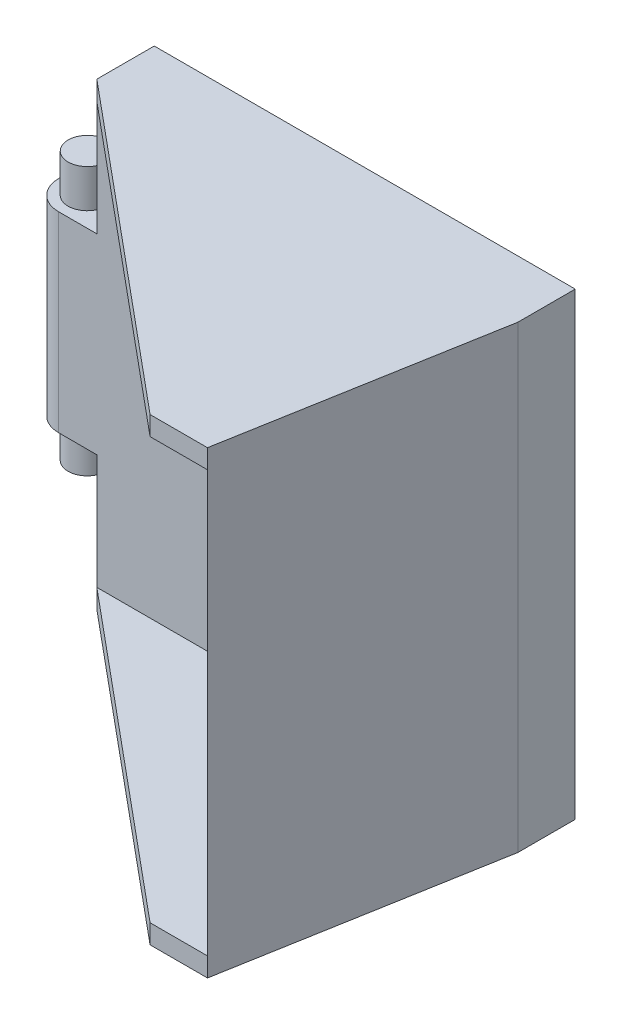
SolidWorks part; units mm, degrees
ref_plane "前视基准面" through (0, 0, 0) normal (0, 0, 1) x (1, 0, 0)
ref_plane "上视基准面" through (0, 0, 0) normal (0, 1, 0) x (1, 0, 0)
ref_plane "右视基准面" through (0, 0, 0) normal (1, 0, 0) x (0, 0, -1)
sketch "草图1" plane through (0, 0, 0) normal (0, 1, 0) x (1, 0, 0)
  line L0 (0, 0) -> (120, 0)
  line L1 (0, 15) -> (120, 15)
  line L7 (120, 15) -> (120, 0)
  arc A1 (0, 0) -> (0, 15) centre (0, 7.5) cw
  circle A3 centre (0, 7.5) radius 5
extrude "凸台-拉伸1" add sketch "草图1" along normal blind 42.5 and the other way blind 7.5
ref_plane "基准面4" through (0, 17.5, 0) normal (0, 1, 0) x (1, 0, 0)
sketch "草图2" plane through (0, 0, 0) normal (0, 1, 0) x (1, 0, 0)
  circle A0 centre (0, 7.5) radius 5
extrude "凸台-拉伸2" add sketch "草图2" against normal mid plane 35
ref_plane "基准面5" through (0, 17.5, 0) normal (0, 1, 0) x (1, 0, 0)
ref_plane "基准面6" through (0, 52.5, 0) normal (0, 1, 0) x (1, 0, 0)
sketch "草图3" plane through (0, 0, 0) normal (0, 1, 0) x (1, 0, 0)
  circle A0 centre (0, 7.5) radius 5
extrude "凸台-拉伸3" add sketch "草图3" along normal up to surface (52.5 mm away) up to plane "基准面6"
ref_plane "基准面7" through (0, 27.5, 0) normal (0, -1, 0) x (-1, 0, 0)
ref_plane "基准面8" through (0, 7.5, 0) normal (0, 1, 0) x (1, 0, 0)
ref_plane "基准面9" through (10, 0, 0) normal (1, 0, 0) x (0, 0, -1)
sketch "草图5" plane through (0, 0, 0) normal (0, 1, 0) x (1, 0, 0)
  line L1 (10, 0) -> (120, 0)
  line L2 (10, 0) -> (10, 15)
  line L3 (10, 15) -> (120, 15)
  line L4 (120, 0) -> (120, 15)
extrude "凸台-拉伸4" add sketch "草图5" along normal blind 77.5 and the other way blind 42.5 contours L1 L4 L3 L2
sketch "草图9" plane through (0, 77.5, 0) normal (0, 1, 0) x (1, 0, 0)
  line L1 (107.8446, -68.9365) -> (92.8446, -68.9365)
  line L2 (92.8446, -68.9365) -> (105, 0)
  line L3 (10, 0) -> (120, 0) construction
  line L4 (105, 0) -> (120, 0)
  line L5 (120, 0) -> (107.8446, -68.9365)
extrude "凸台-拉伸6" add sketch "草图9" against normal up to surface (120 mm away) up to face at (65, -42.5, -7.5)
sketch "草图11" plane through (0, 77.5, 0) normal (0, 1, 0) x (1, 0, 0)
  line L0 (92.8446, -68.9365) -> (10, 0)
  line L1 (10, 0) -> (105, 0)
  line L2 (105, 0) -> (92.8446, -68.9365)
extrude "凸台-拉伸7" add sketch "草图11" against normal blind 5
sketch "草图12" plane through (0, -42.5, 0) normal (0, -1, 0) x (1, 0, 0)
  line L0 (10, 0) -> (92.8446, 68.9365)
  line L1 (92.8446, 68.9365) -> (105, 0)
  line L2 (105, 0) -> (10, 0)
extrude "凸台-拉伸8" add sketch "草图12" against normal blind 5
chamfer "倒角1" distance 15 angle 85 1 edges at (92.8446, 17.5, 68.9365) first distance on face at (97.8446, 17.5, 68.9365)
fillet "圆角1" radius 10 1 edges at (105, 17.5, 0)
